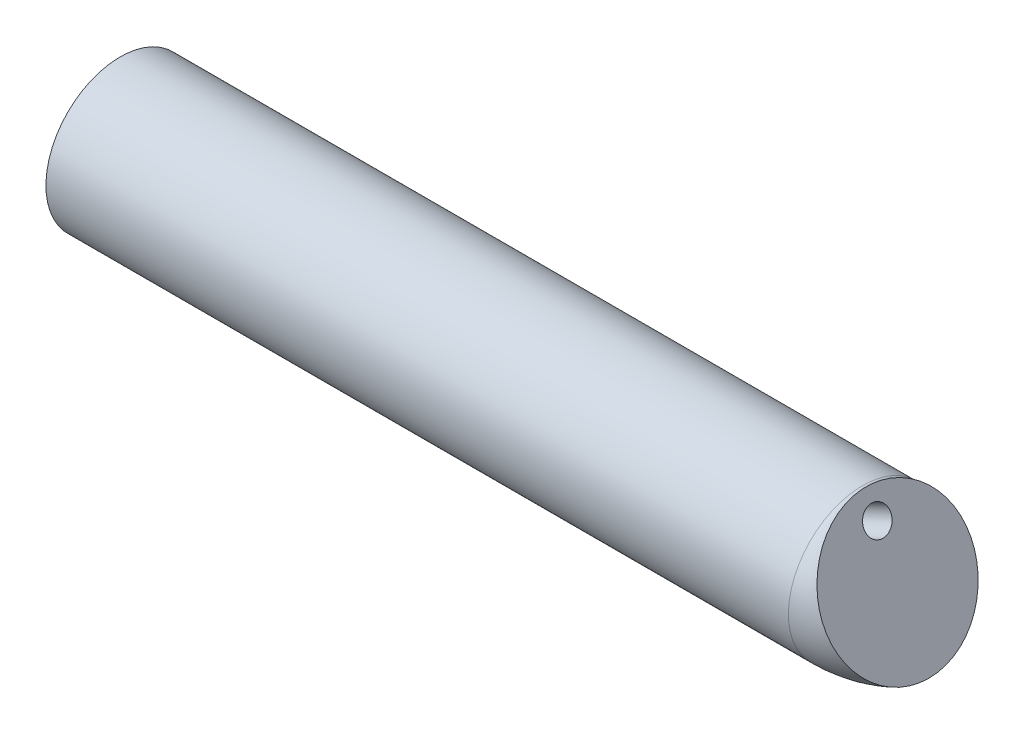
SolidWorks part; units mm, degrees
ref_plane "Alzado" through (0, 0, 0) normal (0, 0, 1) x (1, 0, 0)
ref_plane "Planta" through (0, 0, 0) normal (0, 1, 0) x (1, 0, 0)
ref_plane "Vista lateral" through (0, 0, 0) normal (1, 0, 0) x (0, 0, -1)
sketch "Croquis1" plane through (0, 0, 0) normal (1, 0, 0) x (0, 0, -1)
  circle A0 centre (0, 0) radius 9
  dimension "D1" = 18
extrude "Saliente-Extruir1" add sketch "Croquis1" along normal blind 90
sketch "Croquis2" plane through (90, 0, 0) normal (1, 0, 0) x (0, 0, -1)
  line L0 (-18.2788, 10) -> (25.9849, 10) construction
  circle A1 centre (0, 0) radius 9
  circle A2 centre (0, 0) radius 9
  dimension "D1" = 10
  dimension "D2" = 0
revolve "Revolución1" add sketch "Croquis2" angle 25 about L0 reverse direction yes
sketch "Croquis3" plane through (77.7557, 36.2581, 0) normal (0.9063, 0.4226, 0) x (0, 0, -1)
  circle A1 centre (0, -38.9726) radius 9
  circle A2 centre (0, -38.9726) radius 9
  dimension "D1" = 0
extrude "Saliente-Extruir2" add sketch "Croquis3" along normal blind 140
sketch "Croquis5" plane through (204.6388, 95.4246, 0) normal (0.9063, 0.4226, 0) x (0, 0, -1)
  line L0 (-32.8, -36.8226) -> (-3.0251, -47.4489)
  line L1 (-32.8, -29.8226) -> (32.8, -29.8226)
  line L2 (-32.8, -29.8226) -> (-32.8, -36.8226)
  line L4 (32.8, -29.8226) -> (32.8, -36.8226)
  line L5 (32.8, -36.8226) -> (3.0251, -47.4489)
  circle A1 centre (0, -38.9726) radius 9
  arc A2 (-3.0251, -47.4489) -> (3.0251, -47.4489) centre (0, -38.9726) ccw
  point P7 (0, -29.8226)
  dimension "D2" = 65.6
  dimension "D3" = 7
  dimension "D1" = 0
extrude "Saliente-Extruir3" add sketch "Croquis5" against normal blind 126.6
sketch "Croquis7" plane through (12.6036, -27.0285, 0) normal (-0.4226, 0.9063, 0) x (0.9063, 0.4226, 0)
  line L1 (102.1939, 29.8) -> (222.7939, 29.8)
  line L2 (102.1939, 29.8) -> (102.1939, -29.8)
  line L3 (102.1939, -29.8) -> (222.7939, -29.8)
  line L4 (222.7939, 29.8) -> (222.7939, -29.8)
  line L6 (99.1939, 9) -> (99.1939, -9) construction
  line L7 (99.1939, 32.8) -> (225.7939, 32.8) construction
  point P4 (102.1939, 0)
  point P8 (99.1939, 0)
  point P11 (162.4939, 29.8)
  point P12 (162.4939, 32.8)
  dimension "D1" = 59.6
  dimension "D2" = 120.6
extrude "Cortar-Extruir1" cut sketch "Croquis7" against normal blind 5
fillet "Redondeo2" radius 7.5 4 edges at (215.58, 64.8625, 29.8) (215.58, 64.8625, -29.8) (106.2792, 13.8947, -29.8) (106.2792, 13.8947, 29.8)
fillet "Redondeo1" radius 10.5 4 edges at (218.7215, 65.2241, -32.8) (103.9829, 11.7206, -32.8) (103.9829, 11.7206, 32.8) (218.7215, 65.2241, 32.8)
sketch "Croquis8" plane through (92.6191, 43.189, 0) normal (0.9063, 0.4226, 0) x (0, 0, -1)
  line L0 (22.3, -34.8226) -> (-22.3, -34.8226) construction
  circle A0 centre (0, -33.1726) radius 1.65
  point P5 (0, -34.8226)
  dimension "D1" = 3.3
extrude "Cortar-Extruir2" cut sketch "Croquis8" against normal blind 60
sketch "Croquis9" plane through (12.6036, -27.0285, 0) normal (-0.4226, 0.9063, 0) x (0.9063, 0.4226, 0)
  line L1 (96.1939, 4.3936) -> (99.1939, 4.3936)
  line L2 (96.1939, 4.3936) -> (96.1939, -3.8064)
  line L3 (96.1939, -3.8064) -> (99.1939, -3.8064)
  line L4 (99.1939, 4.3936) -> (99.1939, -3.8064)
  line L5 (99.1939, 22.3) -> (99.1939, -22.3) construction
  dimension "D1" = 8.2
  dimension "D2" = 3
extrude "Cortar-Extruir3" cut sketch "Croquis9" against normal blind 7.6
chamfer "Chaflán1" distance 3 angle 40 2 edges at (106.6883, 5.9189, -8.9686) (106.5492, 6.2173, 8.9901) first distance on face at (94.2262, 0.9369, -9)
sketch "Croquis10" plane through (89.9002, 41.9211, 0) normal (-0.9063, -0.4226, 0) x (0, 0, 1)
  circle A2 centre (0, -33.1726) radius 3.05
  dimension "D1" = 6.1
extrude "Cortar-Extruir4" cut sketch "Croquis10" along normal blind 58.6 from offset 20
chamfer "Chaflán2" distance 1.5 angle 40 9 edges at (102.5038, 14.8927, 14.6474) (105.291, 16.1924, 29.7246) (159.8731, 41.6444, 32.8) (214.4551, 67.0964, 29.7246) (102.5038, 14.8927, -14.6474) (217.2423, 68.3961, 0) (105.291, 16.1924, -29.7246) (214.4551, 67.0964, -29.7246) (159.8731, 41.6444, -32.8) first distance on face at (159.8731, 41.6444, 0)
chamfer "Chaflán3" distance 0.5 angle 70 8 edges at (105.2227, 16.1605, 0) (107.2136, 17.0889, 27.6033) (107.2136, 17.0889, -27.6033) (159.8731, 41.6444, 29.8) (159.8731, 41.6444, -29.8) (212.5325, 66.1999, 27.6033) (212.5325, 66.1999, -27.6033) (214.5234, 67.1283, 0) first distance on face at (135.2686, 30.1711, -0.0629)
sketch "Croquis11" plane through (0, 0, 0) normal (0, 0, 1) x (1, 0, 0)
  line L0 (59.9792, 74.3798) -> (107.4995, -27.5278)
  line L1 (107.4995, -27.5278) -> (244.4121, -27.5278)
  line L2 (244.4121, -27.5278) -> (244.4121, 74.3798)
  line L3 (244.4121, 74.3798) -> (59.9792, 74.3798)
  line L4 (90.4226, 9.0937) -> (98.0297, -7.2198) construction
extrude "Cortar-Extruir7" cut sketch "Croquis11" against normal blind 100 and the other way blind 100
